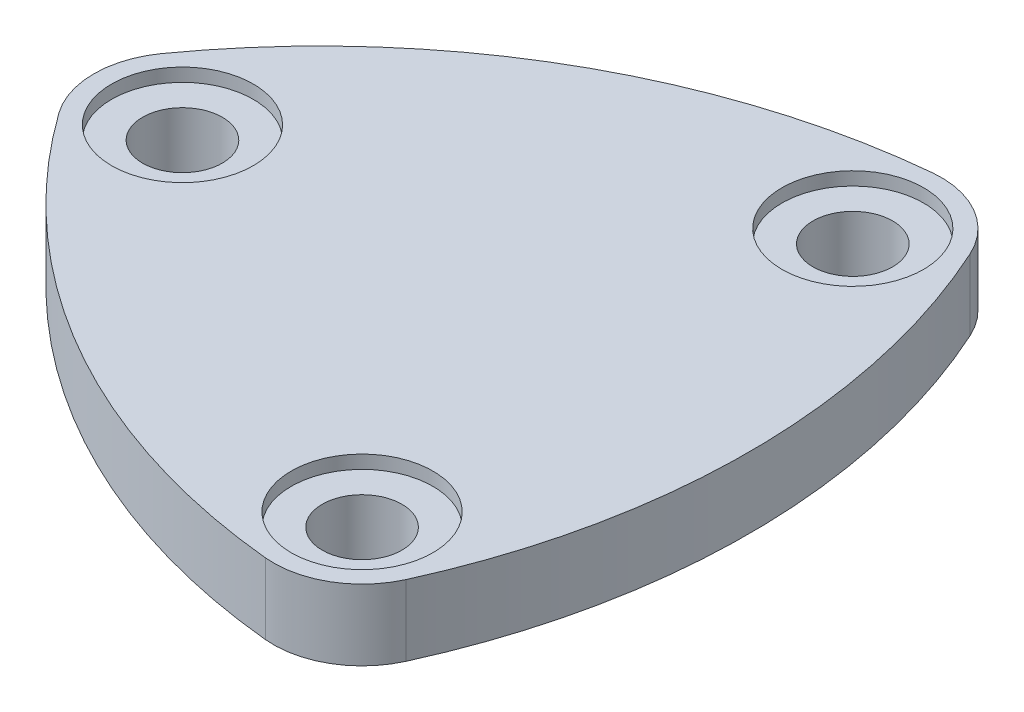
SolidWorks part; units mm, degrees
ref_plane "前基準面" through (0, 0, 0) normal (0, 0, 1) x (1, 0, 0)
ref_plane "上基準面" through (0, 0, 0) normal (0, 1, 0) x (1, 0, 0)
ref_plane "右基準面" through (0, 0, 0) normal (1, 0, 0) x (0, 0, -1)
sketch "草圖1" plane through (0, 0, 0) normal (0, 1, 0) x (1, 0, 0)
  line L0 (0, 0) -> (-56.1893, 0) construction
  line L1 (0, 0) -> (30.5096, 52.8442) construction
  line L2 (0, 0) -> (22.6326, -39.2008) construction
  circle A0 centre (0, 0) radius 32 construction
  circle A1 centre (-32, 0) radius 4.5
  circle A2 centre (16, 27.7128) radius 4.5
  circle A3 centre (-32, 0) radius 10
  circle A4 centre (16, 27.7128) radius 10
  arc A5 (25.1045, -31.8491) -> (25.1045, 31.8491) centre (-45, 0) ccw
  arc A6 (-40.1343, 5.8166) -> (15.0299, 37.6656) centre (22.5, -38.9711) cw
  arc A7 (-40.1343, -5.8166) -> (15.0299, -37.6656) centre (22.5, 38.9711) ccw
  circle A8 centre (16, -27.7128) radius 4.5
  circle A9 centre (16, -27.7128) radius 10
  point P5 (16, 27.7128)
  dimension "D1" = 64
  dimension "D3" = 9
  dimension "D4" = 9
  dimension "D5" = 20
  dimension "D7" = 9
  dimension "D8" = 20
  dimension "D2" = 120
  dimension "D6" = 120
extrude "填料-伸長1" add sketch "草圖1" along normal blind 8 contours A9 A5 A4 A6 A3 A7 region at (0, 0, 0)
extrude "填料-伸長2" add sketch "草圖1<3>" along normal blind 8 contours A9 A8 | A4 A2 | A3 A1 region at (-29.0322, 0, 9.2528) region at (20.8586, 0, -36.1281) region at (9.4707, 0, 20.5162)
sketch "草圖1<3>" plane through (0, 0, 0) normal (0, 1, 0) x (1, 0, 0) same geometry as "草圖1"
sketch "草圖2" plane through (0, 8, 0) normal (0, 1, 0) x (1, 0, 0)
  circle A0 centre (-32, 0) radius 8
  circle A1 centre (16, 27.7128) radius 8
  circle A2 centre (16, -27.7128) radius 8
  dimension "D1" = 16
  dimension "D2" = 16
  dimension "D3" = 16
extrude "除料-伸長1" cut sketch "草圖2" against normal blind 1.5
